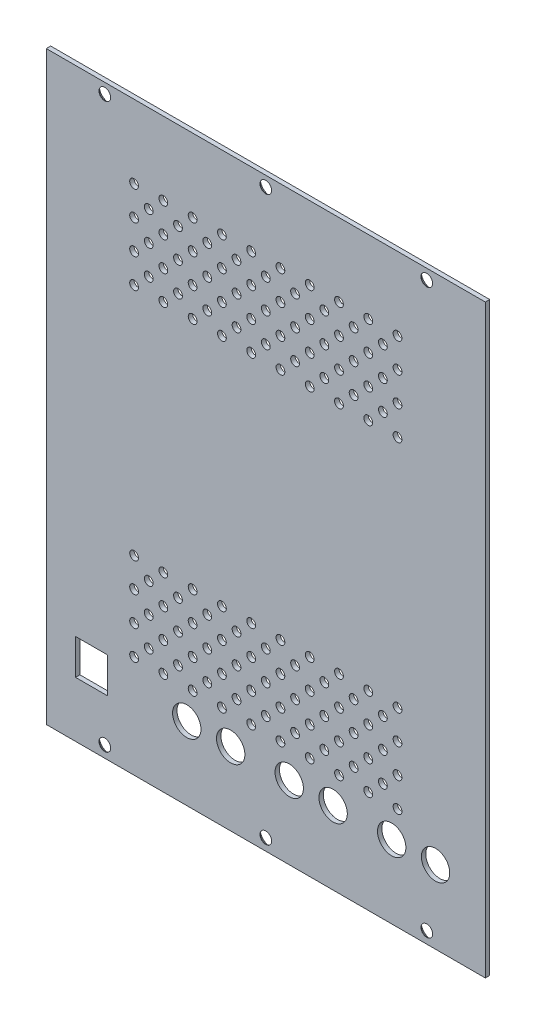
SolidWorks part; units mm, degrees
ref_plane "Спереди" through (0, 0, 0) normal (0, 0, 1) x (1, 0, 0)
ref_plane "Сверху" through (0, 0, 0) normal (0, 1, 0) x (1, 0, 0)
ref_plane "Справа" through (0, 0, 0) normal (1, 0, 0) x (0, 0, -1)
sketch "Эскиз1" plane through (0, 0, 0) normal (0, 0, 1) x (1, 0, 0)
  line L1 (0, 0) -> (150, 0)
  line L2 (0, 0) -> (0, 200)
  line L3 (0, 200) -> (150, 200)
  line L4 (150, 0) -> (150, 200)
  dimension "D1" = 150
  dimension "D2" = 200
extrude "Бобышка-Вытянуть1" add sketch "Эскиз1" along normal blind 1.5
sketch "Эскиз2" plane through (0, 0, 1.5) normal (0, 0, 1) x (1, 0, 0)
  line L0 (0, 0) -> (150, 0) construction
  line L1 (0, 200) -> (0, 0) construction
  line L2 (150, 200) -> (0, 200) construction
  circle A0 centre (20, 196.5) radius 2
  circle A1 centre (20, 4) radius 2
  circle A2 centre (75, 196.5) radius 2
  circle A3 centre (75, 4) radius 2
  circle A4 centre (130, 196.5) radius 2
  circle A5 centre (130, 4) radius 2
  dimension "D1" = 4
  dimension "D2" = 4
  dimension "D3" = 20
  dimension "D4" = 3.5
  dimension "D5" = 3
extrude "Вырез-Вытянуть1" cut sketch "Эскиз2" against normal through all
sketch "Эскиз3" plane through (0, 0, 1.5) normal (0, 0, 1) x (1, 0, 0)
  line L0 (0, 200) -> (0, 0) construction
  line L1 (0, 0) -> (150, 0) construction
  circle A0 centre (30, 35) radius 1.5
  circle A1 centre (40, 35) radius 1.5
  circle A2 centre (50, 35) radius 1.5
  circle A3 centre (60, 35) radius 1.5
  circle A4 centre (70, 35) radius 1.5
  circle A5 centre (80, 35) radius 1.5
  circle A6 centre (90, 35) radius 1.5
  circle A7 centre (100, 35) radius 1.5
  circle A8 centre (110, 35) radius 1.5
  circle A9 centre (120, 35) radius 1.5
  circle A10 centre (30, 45) radius 1.5
  circle A11 centre (40, 45) radius 1.5
  circle A12 centre (50, 45) radius 1.5
  circle A13 centre (60, 45) radius 1.5
  circle A14 centre (70, 45) radius 1.5
  circle A15 centre (80, 45) radius 1.5
  circle A16 centre (90, 45) radius 1.5
  circle A17 centre (100, 45) radius 1.5
  circle A18 centre (110, 45) radius 1.5
  circle A19 centre (120, 45) radius 1.5
  circle A20 centre (30, 55) radius 1.5
  circle A21 centre (40, 55) radius 1.5
  circle A22 centre (50, 55) radius 1.5
  circle A23 centre (60, 55) radius 1.5
  circle A24 centre (70, 55) radius 1.5
  circle A25 centre (80, 55) radius 1.5
  circle A26 centre (90, 55) radius 1.5
  circle A27 centre (100, 55) radius 1.5
  circle A28 centre (110, 55) radius 1.5
  circle A29 centre (120, 55) radius 1.5
  circle A30 centre (30, 65) radius 1.5
  circle A31 centre (40, 65) radius 1.5
  circle A32 centre (50, 65) radius 1.5
  circle A33 centre (60, 65) radius 1.5
  circle A34 centre (70, 65) radius 1.5
  circle A35 centre (80, 65) radius 1.5
  circle A36 centre (90, 65) radius 1.5
  circle A37 centre (100, 65) radius 1.5
  circle A38 centre (110, 65) radius 1.5
  circle A39 centre (120, 65) radius 1.5
  circle A40 centre (35, 40) radius 1.5
  circle A41 centre (45, 40) radius 1.5
  circle A42 centre (55, 40) radius 1.5
  circle A43 centre (65, 40) radius 1.5
  circle A44 centre (75, 40) radius 1.5
  circle A45 centre (85, 40) radius 1.5
  circle A46 centre (95, 40) radius 1.5
  circle A47 centre (105, 40) radius 1.5
  circle A48 centre (115, 40) radius 1.5
  circle A49 centre (45, 50) radius 1.5
  circle A50 centre (55, 50) radius 1.5
  circle A51 centre (65, 50) radius 1.5
  circle A52 centre (75, 50) radius 1.5
  circle A53 centre (85, 50) radius 1.5
  circle A54 centre (95, 50) radius 1.5
  circle A55 centre (105, 50) radius 1.5
  circle A56 centre (115, 50) radius 1.5
  circle A57 centre (45, 60) radius 1.5
  circle A58 centre (55, 60) radius 1.5
  circle A59 centre (65, 60) radius 1.5
  circle A60 centre (75, 60) radius 1.5
  circle A61 centre (85, 60) radius 1.5
  circle A62 centre (95, 60) radius 1.5
  circle A63 centre (105, 60) radius 1.5
  circle A64 centre (115, 60) radius 1.5
  circle A65 centre (35, 50) radius 1.5
  circle A66 centre (35, 60) radius 1.5
  circle A67 centre (30, 145) radius 1.5
  circle A68 centre (40, 145) radius 1.5
  circle A69 centre (50, 145) radius 1.5
  circle A70 centre (60, 145) radius 1.5
  circle A71 centre (70, 145) radius 1.5
  circle A72 centre (80, 145) radius 1.5
  circle A73 centre (90, 145) radius 1.5
  circle A74 centre (100, 145) radius 1.5
  circle A75 centre (110, 145) radius 1.5
  circle A76 centre (120, 145) radius 1.5
  circle A77 centre (30, 155) radius 1.5
  circle A78 centre (40, 155) radius 1.5
  circle A79 centre (50, 155) radius 1.5
  circle A80 centre (60, 155) radius 1.5
  circle A81 centre (70, 155) radius 1.5
  circle A82 centre (80, 155) radius 1.5
  circle A83 centre (90, 155) radius 1.5
  circle A84 centre (100, 155) radius 1.5
  circle A85 centre (110, 155) radius 1.5
  circle A86 centre (120, 155) radius 1.5
  circle A87 centre (30, 165) radius 1.5
  circle A88 centre (40, 165) radius 1.5
  circle A89 centre (50, 165) radius 1.5
  circle A90 centre (60, 165) radius 1.5
  circle A91 centre (70, 165) radius 1.5
  circle A92 centre (80, 165) radius 1.5
  circle A93 centre (90, 165) radius 1.5
  circle A94 centre (100, 165) radius 1.5
  circle A95 centre (110, 165) radius 1.5
  circle A96 centre (120, 165) radius 1.5
  circle A97 centre (30, 175) radius 1.5
  circle A98 centre (40, 175) radius 1.5
  circle A99 centre (50, 175) radius 1.5
  circle A100 centre (60, 175) radius 1.5
  circle A101 centre (70, 175) radius 1.5
  circle A102 centre (80, 175) radius 1.5
  circle A103 centre (90, 175) radius 1.5
  circle A104 centre (100, 175) radius 1.5
  circle A105 centre (110, 175) radius 1.5
  circle A106 centre (120, 175) radius 1.5
  circle A107 centre (35, 150) radius 1.5
  circle A108 centre (45, 150) radius 1.5
  circle A109 centre (55, 150) radius 1.5
  circle A110 centre (65, 150) radius 1.5
  circle A111 centre (75, 150) radius 1.5
  circle A112 centre (85, 150) radius 1.5
  circle A113 centre (95, 150) radius 1.5
  circle A114 centre (105, 150) radius 1.5
  circle A115 centre (115, 150) radius 1.5
  circle A116 centre (45, 160) radius 1.5
  circle A117 centre (55, 160) radius 1.5
  circle A118 centre (65, 160) radius 1.5
  circle A119 centre (75, 160) radius 1.5
  circle A120 centre (85, 160) radius 1.5
  circle A121 centre (95, 160) radius 1.5
  circle A122 centre (105, 160) radius 1.5
  circle A123 centre (115, 160) radius 1.5
  circle A124 centre (45, 170) radius 1.5
  circle A125 centre (55, 170) radius 1.5
  circle A126 centre (65, 170) radius 1.5
  circle A127 centre (75, 170) radius 1.5
  circle A128 centre (85, 170) radius 1.5
  circle A129 centre (95, 170) radius 1.5
  circle A130 centre (105, 170) radius 1.5
  circle A131 centre (115, 170) radius 1.5
  circle A132 centre (35, 160) radius 1.5
  circle A133 centre (35, 170) radius 1.5
  dimension "D1" = 3
  dimension "D2" = 30
  dimension "D3" = 35
  dimension "D5" = 4
  dimension "D6" = 5
  dimension "D7" = 5
  dimension "D4" = 10
  dimension "D8" = 9
  dimension "D9" = 3
  dimension "D10" = 2
extrude "Вырез-Вытянуть2" cut sketch "Эскиз3" against normal through all
sketch "Эскиз4" plane through (0, 0, 0) normal (0, 0, -1) x (-1, 0, 0)
  line L0 (-150, 0) -> (-150, 200) construction
  line L1 (0, 0) -> (-150, 0) construction
  circle A0 centre (-48, 25) radius 4.85
  circle A1 centre (-133, 25) radius 4.85
  circle A2 centre (-118, 25) radius 4.85
  circle A3 centre (-83, 25) radius 4.85
  circle A4 centre (-98, 25) radius 4.85
  circle A5 centre (-63, 25) radius 4.85
  dimension "D1" = 9.7
  dimension "D2" = 17
  dimension "D3" = 25
  dimension "D4" = 2
  dimension "D5" = 3
extrude "Вырез-Вытянуть3" cut sketch "Эскиз4" against normal through all
sketch "Эскиз5" plane through (0, 0, 0) normal (0, 0, -1) x (-1, 0, 0)
  line L0 (-131, 13) -> (-116.6472, 13) construction
  line L1 (-96, 13) -> (-81.6472, 13) construction
  line L2 (0, 0) -> (-150, 0) construction
  line L3 (-73, 13) -> (-10.6742, 13) construction
  circle A0 centre (-133, 25) radius 4.85 construction
  circle A1 centre (-98, 25) radius 4.85 construction
  circle A2 centre (-63, 25) radius 4.85 construction
  text T0 "24V" font "GOST Type BU" height 5
  text T1 "10V" font "GOST type B" height 5
  text T2 "мультиметр" font "GOST type B" height 5
  dimension "D1" = 13
  dimension "D2" = 2
  dimension "D3" = 2
  dimension "D4" = 10
extrude "Вырез-Вытянуть4" cut sketch "Эскиз5" against normal blind 0.5
sketch "Эскиз8" plane through (0, 0, 0) normal (0, 0, -1) x (-1, 0, 0)
  line L0 (0, 200) -> (0, 0) construction
  line L1 (-21, 31.05) -> (-10, 31.05)
  line L2 (-21, 31.05) -> (-21, 18.95)
  line L3 (-21, 18.95) -> (-10, 18.95)
  line L4 (-10, 31.05) -> (-10, 18.95)
  circle A1 centre (-48, 25) radius 4.85 construction
  point P6 (-21, 25)
  dimension "D1" = 10
  dimension "D2" = 0
  dimension "D3" = 11
  dimension "D4" = 12.1
extrude "Вырез-Вытянуть5" cut sketch "Эскиз8" against normal through all
sketch "Эскиз9" plane through (0, 0, 0) normal (0, 0, -1) x (-1, 0, 0)
  line L0 (-22.5, 10.95) -> (-5.209, 10.95) construction
  line L1 (-21, 18.95) -> (-10, 18.95) construction
  line L2 (-21, 31.05) -> (-21, 18.95) construction
  text T0 "USB" font "GOST type B" height 6
  dimension "D1" = 8
  dimension "D2" = 1.5
extrude "Вырез-Вытянуть6" cut sketch "Эскиз9" against normal up to surface (0.5 mm away) up to face at (36.6786, 14.7184, 0.5)
chamfer "Фаска1" distance 1.4 angle 45 6 edges at (22, 4, 0) (77, 4, 0) (132, 4, 0) (22, 196.5, 0) (77, 196.5, 0) (132, 196.5, 0)
